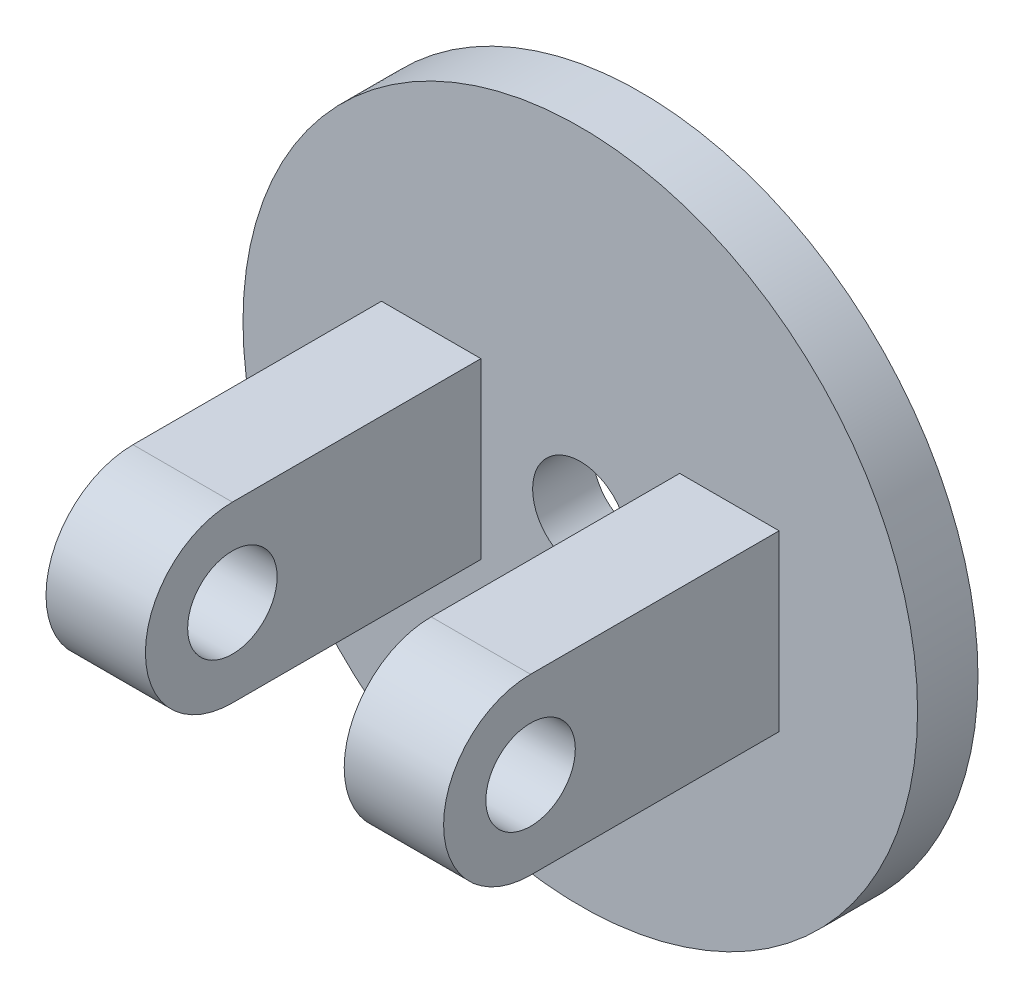
SolidWorks part; units mm, degrees
ref_plane "Front Plane" through (0, 0, 0) normal (0, 0, 1) x (1, 0, 0)
ref_plane "Top Plane" through (0, 0, 0) normal (0, 1, 0) x (1, 0, 0)
ref_plane "Right Plane" through (0, 0, 0) normal (1, 0, 0) x (0, 0, -1)
sketch "Sketch4" plane through (0, 0, 0) normal (0, 1, 0) x (1, 0, 0)
  line L0 (-73.5426, 0) -> (70.9621, 0) construction
  line L1 (0, 85.5416) -> (0, -95.0893) construction
  line L2 (0, 0) -> (0, -18.4502)
  line L3 (0, -18.4502) -> (67.8656, -18.4502)
  line L4 (67.8656, -18.4502) -> (67.8656, 58.705)
  line L5 (67.8656, 58.705) -> (49.0284, 58.705)
  line L6 (49.0284, 58.705) -> (49.0284, 0)
  line L7 (49.0284, 0) -> (0, 0)
revolve "Revolve1" add sketch "Sketch4" angle 360 about L1
sketch "Sketch5" plane through (0, 0, 0) normal (0, 0, -1) x (-1, 0, 0)
  circle A0 centre (0, 0) radius 9.5899
extrude "Cut-Extrude1" cut sketch "Sketch5" against normal blind 40
ref_plane "Plane2" through (0, 0, 18.4502) normal (0, 0, 1) x (1, 0, 0)
ref_plane "Plane3" through (0, 0, -58.705) normal (0, 0, -1) x (-1, 0, 0)
ref_plane "Plane4" through (0, 0, -20.1274) normal (0, 0, -1) x (-1, 0, 0)
sketch "Sketch6" plane through (0, 0, -58.705) normal (0, 0, -1) x (-1, 0, 0)
  line L0 (-8.3621, 48.31) -> (-5.8971, 44.6317)
  line L1 (-5.8971, 44.6317) -> (-3.6128, 45.1811)
  line L2 (-3.6128, 45.1811) -> (-2.682, 48.955)
  line L3 (-2.682, 48.955) -> (-8.3621, 48.31)
  circle A1 centre (0, 0) radius 49.0284 construction
extrude "Boss-Extrude8" add sketch "Sketch6" against normal blind 60 separate body
ref_axis "Axis1" through (0, 0, 18.4502) along (0, 0, -1)
pattern_circular "CirPattern8" count 24 every 15 about axis through (0, 0, 18.4502) along (0, 0, -1) of bodies 105
sketch "Sketch18" plane through (0, 0, 18.4502) normal (0, 0, 1) x (1, 0, 0)
  line L0 (-67.8656, 0) -> (67.8656, 0) construction
  line L1 (0, 0) -> (0, 67.8656) construction
  line L2 (0, 0) -> (-40, 0) construction
  line L3 (-40, 0) -> (40, 0) construction
  line L5 (-40, -17.5) -> (-20, -17.5)
  line L6 (-40, -17.5) -> (-40, 17.5)
  line L7 (-40, 17.5) -> (-20, 17.5)
  line L8 (-20, -17.5) -> (-20, 17.5)
  line L9 (40, 17.5) -> (20, 17.5)
  line L10 (40, 17.5) -> (40, -17.5)
  line L11 (40, -17.5) -> (20, -17.5)
  line L12 (20, 17.5) -> (20, -17.5)
  circle A0 centre (0, 0) radius 67.8656 construction
  dimension "D1" = 40
  dimension "D2" = 40
  dimension "D3" = 20
  dimension "D4" = 35
  dimension "D5" = 17.5
  dimension "D6" = 0
  dimension "D7" = 20
  dimension "D8" = 35
  dimension "D9" = 40
  dimension "D10" = 17.5
extrude "Boss-Extrude9" add sketch "Sketch18" along normal blind 50
sketch "Sketch19" plane through (-20, 0, 0) normal (1, 0, 0) x (0, 0, -1)
  line L0 (-68.4502, -17.5) -> (-68.4502, 17.5) construction
  circle A0 centre (-68.4502, 0) radius 17.5
extrude "Boss-Extrude10" add sketch "Sketch19" against normal blind 20
sketch "Sketch20" plane through (40, 0, 0) normal (1, 0, 0) x (0, 0, -1)
  line L0 (-68.4502, -17.5) -> (-68.4502, 17.5) construction
  circle A0 centre (-68.4502, 0) radius 17.5
extrude "Boss-Extrude11" add sketch "Sketch20" against normal blind 20
sketch "Sketch22" plane through (0, 0, -58.705) normal (0, 0, -1) x (-1, 0, 0)
  circle A0 centre (0, 0) radius 70
  dimension "D1" = 140
extrude "Cut-Extrude3" cut sketch "Sketch22" against normal blind 65
sketch "Sketch23" plane through (40, 0, 0) normal (1, 0, 0) x (0, 0, -1)
  line L0 (-68.4502, -17.5) -> (-18.4502, -17.5) construction
  line L1 (-18.4502, -17.5) -> (-18.4502, 17.5) construction
  circle A1 centre (-68.4502, 0) radius 9
  dimension "D1" = 17.5
  dimension "D3" = 18
  dimension "D2" = 50
extrude "Cut-Extrude4" cut sketch "Sketch23" against normal blind 90
